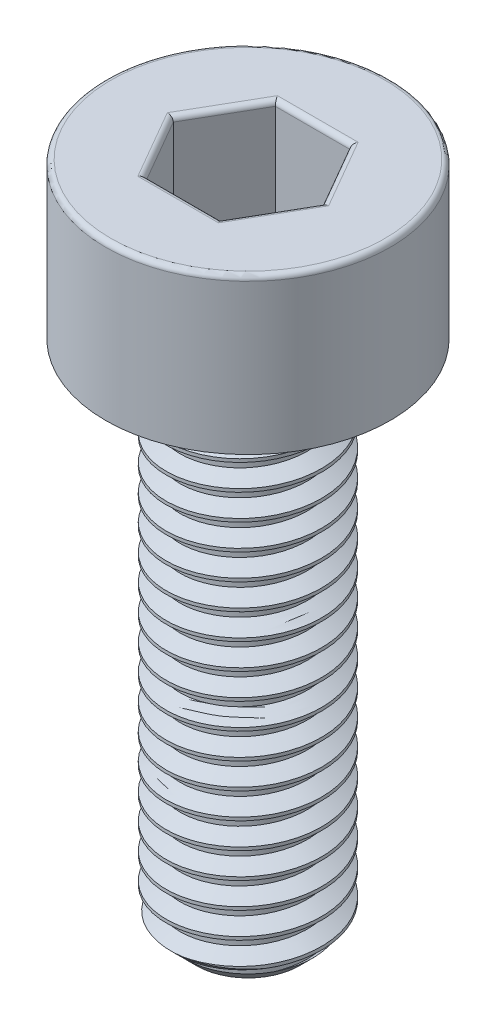
SolidWorks part; units mm, degrees
material "AISI 304"
ref_plane "Plano frontal" through (0, 0, 0) normal (0, 0, 1) x (1, 0, 0)
ref_plane "Plano superior" through (0, 0, 0) normal (0, 1, 0) x (1, 0, 0)
ref_plane "Plano direito" through (0, 0, 0) normal (1, 0, 0) x (0, 0, -1)
sketch "Esboço1" plane through (0, 0, 0) normal (0, 1, 0) x (1, 0, 0)
  circle A0 centre (0, 0) radius 2.75
  dimension "D1" = 5.5
extrude "Ressalto-extrusão1" add sketch "Esboço1" along normal blind 3 contours A0
sketch "Esboço3" plane through (0, 3, 0) normal (0, 1, 0) x (1, 0, 0)
  line L1 (1.4434, 0) -> (0.7217, 1.25)
  line L2 (0.7217, 1.25) -> (-0.7217, 1.25)
  line L3 (-0.7217, 1.25) -> (-1.4434, 0)
  line L4 (-1.4434, 0) -> (-0.7217, -1.25)
  line L5 (-0.7217, -1.25) -> (0.7217, -1.25)
  line L6 (0.7217, -1.25) -> (1.4434, 0)
  circle A0 centre (0, 0) radius 1.25 construction
  dimension "D1" = 2.5
extrude "Corte-extrusão1" cut sketch "Esboço3" against normal blind 2.5
chamfer "Chanfro3" distance 0.4 angle 70 6 edges at (0, 0.5, 1.25) (-1.0825, 0.5, 0.625) (-1.0825, 0.5, -0.625) (0, 0.5, -1.25) (1.0825, 0.5, -0.625) (1.0825, 0.5, 0.625) first distance on face at (0, 1.75, 1.25) first distance on face at (-1.0825, 1.75, 0.625) first distance on face at (-1.0825, 1.75, -0.625) first distance on face at (0, 1.75, -1.25) first distance on face at (1.0825, 1.75, -0.625) first distance on face at (1.0825, 1.75, 0.625)
fillet "Filete1" radius 0.1 7 edges at (0, 3, 2.75) (1.0825, 3, -0.625) (0, 3, -1.25) (-1.0825, 3, -0.625) (-1.0825, 3, 0.625) (0, 3, 1.25) (1.0825, 3, 0.625)
sketch "Esboço4" plane through (0, 0, 0) normal (0, -1, 0) x (1, 0, 0)
  circle A0 centre (0, 0) radius 1.5
  dimension "D1" = 3
extrude "Ressalto-extrusão2" add sketch "Esboço4" along normal blind 10
chamfer "Chanfro4" distance 0.5 angle 45 1 edges at (0, -10, -1.5)
fillet "Filete2" radius 0.2 1 edges at (0, 0, -1.5)
thread "Rosca1" pitch 0.5 method cut profile "Perfil da rosca1" start angle 0, offset 0, length 0, pitch 0.5, diameter 3
ref_plane "Plano1" through (-1.5, -0.2, 0) normal (0, 0, 1) x (-1, 0, 0)
sketch "Perfil da rosca1" plane through (-1.5, -0.2, 0) normal (0, 0, 1) x (-1, 0, 0)
  line L0 (0, 0) -> (0, 0.5) construction
  line L11 (0, 0) -> (0, 0.4375)
  line L12 (0, 0.4375) -> (-0.2706, 0.2812)
  line L13 (-0.2706, 0.2812) -> (-0.2706, 0.1562)
  line L15 (-0.2706, 0.1562) -> (0, 0)
  line L17 (-0.2706, 0.2187) -> (0, 0.2187) construction
  point P2 (0, 0)
  dimension "Pitch" = 0.5
  dimension "Profile_Angle" = 60
  dimension "Profile_Land" = 0.125
  dimension "Profile_Height" = 0.2706
